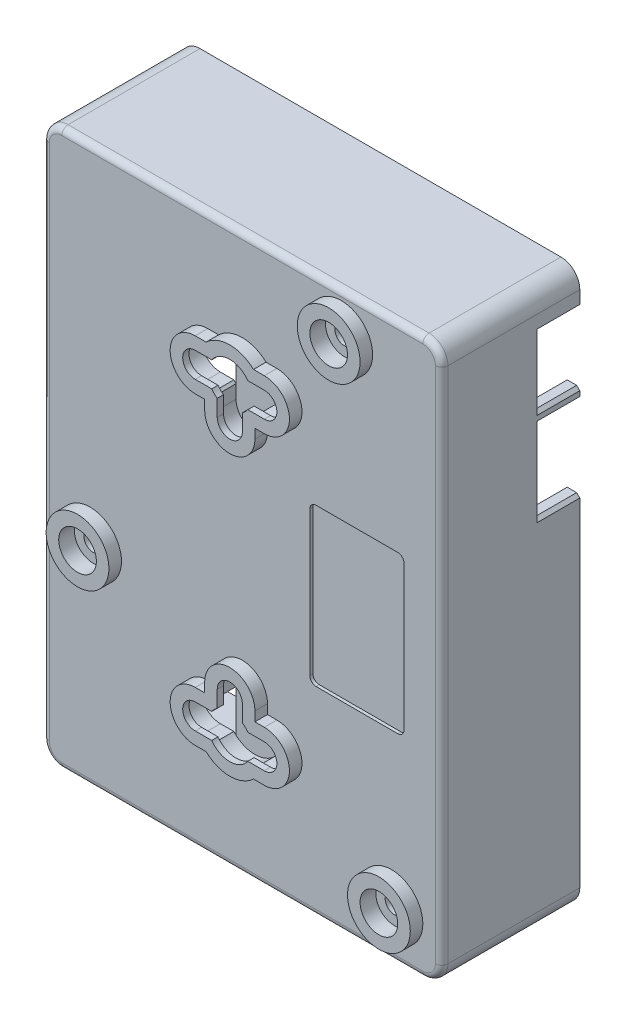
SolidWorks part; units mm, degrees
ref_plane "Front Plane" through (0, 0, 0) normal (0, 0, 1) x (1, 0, 0)
ref_plane "Top Plane" through (0, 0, 0) normal (0, 1, 0) x (1, 0, 0)
ref_plane "Right Plane" through (0, 0, 0) normal (1, 0, 0) x (0, 0, -1)
ref_plane "Plane1" through (0, 0, 2) normal (0, 0, 1) x (1, 0, 0)
sketch "Sketch2" plane through (0, 0, 2) normal (0, 0, 1) x (1, 0, 0)
  line L1 (-39.8212, 60.2968) -> (23.6788, 60.2968)
  line L2 (-39.8212, 60.2968) -> (-39.8212, -28.2032)
  line L3 (-39.8212, -28.2032) -> (23.6788, -28.2032)
  line L4 (23.6788, 60.2968) -> (23.6788, -28.2032)
  line L9 (20.6788, 57.2968) -> (20.6788, -25.2032) construction
  line L10 (20.6788, -25.2032) -> (-36.8212, -25.2032) construction
  line L11 (-36.8212, -25.2032) -> (-36.8212, 57.2968) construction
  line L12 (-36.8212, 57.2968) -> (20.6788, 57.2968) construction
  point P12 (0, 0)
  point P13 (0, 0)
  point P14 (0, 0)
  point P15 (0, 0)
  dimension "D1" = 3
  dimension "D2" = 3
  dimension "D3" = 3
  dimension "D4" = 3
extrude "Boss-Extrude1" add sketch "Sketch2" along normal blind 2
sketch "Sketch3" plane through (0, 0, 2) normal (0, 0, -1) x (-1, 0, 0)
  line L4 (39.8212, -28.2032) -> (39.8212, 60.2968)
  line L5 (39.8212, 60.2968) -> (-23.6788, 60.2968)
  line L6 (-23.6788, 60.2968) -> (-23.6788, -28.2032)
  line L7 (-23.6788, -28.2032) -> (39.8212, -28.2032)
  line L8 (39.8212, -28.2032) -> (39.8212, 60.2968)
  line L9 (39.8212, 60.2968) -> (-23.6788, 60.2968)
  line L10 (-23.6788, 60.2968) -> (-23.6788, -28.2032)
  line L11 (-23.6788, -28.2032) -> (39.8212, -28.2032)
  line L16 (37.8212, -26.2032) -> (37.8212, 58.2968)
  line L17 (37.8212, 58.2968) -> (-21.6788, 58.2968)
  line L18 (-21.6788, 58.2968) -> (-21.6788, -26.2032)
  line L19 (-21.6788, -26.2032) -> (37.8212, -26.2032)
  line L20 (37.8212, -26.2032) -> (37.8212, 58.2968)
  line L21 (37.8212, 58.2968) -> (-21.6788, 58.2968)
  line L22 (-21.6788, 58.2968) -> (-21.6788, -26.2032)
  line L23 (-21.6788, -26.2032) -> (37.8212, -26.2032)
  dimension "D1" = 0
  dimension "D2" = 2
extrude "Boss-Extrude2" add sketch "Sketch3" along normal blind 20
sketch "Sketch4" plane through (23.6788, 0, 0) normal (1, 0, 0) x (0, 0, -1)
  line L0 (18, 60.2968) -> (18, -28.2032) construction
  line L1 (18, 29.0468) -> (11.65, 29.0468)
  line L2 (18, 29.0468) -> (18, 42.0468)
  line L3 (18, 42.0468) -> (11.65, 42.0468)
  line L4 (11.65, 29.0468) -> (11.65, 42.0468)
  line L7 (18, 43.8468) -> (11.65, 43.8468)
  line L8 (18, 43.8468) -> (18, 54.7468)
  line L9 (18, 54.7468) -> (11.65, 54.7468)
  line L10 (11.65, 43.8468) -> (11.65, 54.7468)
  line L11 (16.95, 47.7968) -> (16.95, 50.7968) construction
  line L12 (16.95, 32.7968) -> (16.95, 38.2968) construction
  point P6 (0, 0)
  point P7 (0, 0)
  point P16 (16.95, 49.2968)
  point P17 (11.65, 49.2968)
  point P18 (16.95, 35.5468)
  point P19 (11.65, 35.5468)
  point P20 (0, 0)
  point P21 (0, 0)
  dimension "D1" = 10.9
  dimension "D2" = 13
extrude "Cut-Extrude1" cut sketch "Sketch4" against normal up to surface (2 mm away) up to face at (21.6788, 16.0468, -8)
chamfer "Chamfer1" distance 0.5 angle 45 6 edges at (23.6788, 54.7468, -14.825) (23.6788, 49.2968, -11.65) (23.6788, 43.8468, -14.825) (23.6788, 42.0468, -14.825) (23.6788, 35.5468, -11.65) (23.6788, 29.0468, -14.825)
sketch "Sketch5" plane through (-39.8212, 0, 0) normal (-1, 0, 0) x (0, 0, 1)
  line L0 (-18, -28.2032) -> (-18, 60.2968) construction
  line L1 (4, 60.2968) -> (-18, 60.2968) construction
  line L3 (-18, 34.207) -> (-11.65, 34.207)
  line L4 (-18, 34.207) -> (-18, 9.207)
  line L5 (-18, 9.207) -> (-11.65, 9.207)
  line L6 (-11.65, 34.207) -> (-11.65, 9.207)
  circle A0 centre (-12.432, 40.6543) radius 0.75
  point P12 (0, 0)
  dimension "D1" = 1.5
  dimension "D2" = 5.568
  dimension "D3" = 19.6425
  dimension "D4" = 25
extrude "Cut-Extrude3" cut sketch "Sketch5" against normal up to surface (2 mm away) up to face at (-37.8212, 16.0468, -8)
fillet "Fillet1" radius 6 2 edges at (-38.8212, 9.207, -18) (-38.8212, 34.207, -18)
sketch "Sketch6" plane through (0, -28.2032, 0) normal (0, -1, 0) x (1, 0, 0)
  line L0 (23.6788, -18) -> (-39.8212, -18) construction
  line L1 (13.0098, -18) -> (-13.7903, -18)
  line L2 (13.0098, -18) -> (13.0098, -11.65)
  line L3 (13.0098, -11.65) -> (-13.7903, -11.65)
  line L4 (-13.7903, -18) -> (-13.7903, -11.65)
  point P8 (0, 0)
extrude "Cut-Extrude4" cut sketch "Sketch6" against normal up to surface (2 mm away) up to face at (-8.0712, -26.2032, -8)
fillet "Fillet2" radius 3 4 edges at (-39.8212, 60.2968, -7) (23.6788, 60.2968, -7) (23.6788, -28.2032, -7) (-39.8212, -28.2032, -7)
sketch "Sketch7" plane through (0, 0, 4) normal (0, 0, 1) x (1, 0, 0)
  line L0 (-8.0712, -28.2032) -> (-8.0712, 60.2968) construction
  line L1 (-36.8212, -28.2032) -> (20.6788, -28.2032) construction
  line L2 (20.6788, 60.2968) -> (-36.8212, 60.2968) construction
  line L3 (-2.5712, -8.2032) -> (-13.5712, -8.2032) construction
  line L4 (-2.5712, -10.2032) -> (-5.199, -10.2032)
  line L5 (-2.5712, -6.2032) -> (-5.199, -6.2032)
  line L6 (23.6788, 16.0468) -> (-39.8212, 16.0468) construction
  line L7 (23.6788, -25.2032) -> (23.6788, 57.2968) construction
  line L8 (-39.8212, 57.2968) -> (-39.8212, -25.2032) construction
  line L9 (-10.0712, -2.7032) -> (-10.0712, -5.3309)
  line L10 (-6.0712, -2.7032) -> (-6.0712, -5.3309)
  line L11 (-10.9435, -6.2032) -> (-13.5712, -6.2032)
  line L12 (-10.9435, -10.2032) -> (-13.5712, -10.2032)
  line L13 (-6.0712, 34.7968) -> (-6.0712, 37.4245)
  line L14 (-2.5712, 38.2968) -> (-5.199, 38.2968)
  line L15 (-2.5712, 42.2968) -> (-5.199, 42.2968)
  line L16 (-10.9435, 42.2968) -> (-13.5712, 42.2968)
  line L17 (-10.9435, 38.2968) -> (-13.5712, 38.2968)
  line L18 (-10.0712, 34.7968) -> (-10.0712, 37.4245)
  arc A0 (-2.5712, -10.2032) -> (-2.5712, -6.2032) centre (-2.5712, -8.2032) ccw
  arc A1 (-13.5712, -6.2032) -> (-13.5712, -10.2032) centre (-13.5712, -8.2032) ccw
  arc A2 (-6.0712, -2.7032) -> (-10.0712, -2.7032) centre (-8.0712, -2.7032) ccw
  arc A3 (-10.0712, -5.3309) -> (-10.9435, -6.2032) centre (-8.0712, -8.2032) ccw
  arc A4 (-5.199, -6.2032) -> (-6.0712, -5.3309) centre (-8.0712, -8.2032) ccw
  arc A5 (-10.9435, -10.2032) -> (-5.199, -10.2032) centre (-8.0712, -8.2032) ccw
  arc A6 (-6.0712, 34.7968) -> (-10.0712, 34.7968) centre (-8.0712, 34.7968) cw
  arc A7 (-5.199, 38.2968) -> (-6.0712, 37.4245) centre (-8.0712, 40.2968) cw
  arc A8 (-2.5712, 42.2968) -> (-2.5712, 38.2968) centre (-2.5712, 40.2968) cw
  arc A9 (-10.9435, 42.2968) -> (-5.199, 42.2968) centre (-8.0712, 40.2968) cw
  arc A10 (-13.5712, 38.2968) -> (-13.5712, 42.2968) centre (-13.5712, 40.2968) cw
  arc A11 (-10.0712, 37.4245) -> (-10.9435, 38.2968) centre (-8.0712, 40.2968) cw
  point P8 (-8.0712, -8.2032)
  dimension "D4" = 4
  dimension "D6" = 7
  dimension "D1" = 11
  dimension "D2" = 4
  dimension "D3" = 20
  dimension "D5" = 5.5
extrude "Cut-Extrude5" cut sketch "Sketch7" against normal blind 10
sketch "Sketch8" plane through (0, 0, 4) normal (0, 0, 1) x (1, 0, 0)
  line L0 (-2.5712, 42.2968) -> (-5.199, 42.2968) construction
  line L1 (-5.199, 38.2968) -> (-2.5712, 38.2968) construction
  line L2 (-6.0712, 34.7968) -> (-6.0712, 37.4245) construction
  line L3 (-10.0712, 37.4245) -> (-10.0712, 34.7968) construction
  line L4 (-13.5712, 38.2968) -> (-10.9435, 38.2968) construction
  line L5 (-10.9435, 42.2968) -> (-13.5712, 42.2968) construction
  line L6 (-2.5712, 42.2968) -> (-5.199, 42.2968)
  line L7 (-5.199, 38.2968) -> (-2.5712, 38.2968)
  line L8 (-6.0712, 34.7968) -> (-6.0712, 37.4245)
  line L9 (-10.0712, 37.4245) -> (-10.0712, 34.7968)
  line L10 (-13.5712, 38.2968) -> (-10.9435, 38.2968)
  line L11 (-10.9435, 42.2968) -> (-13.5712, 42.2968)
  line L12 (-11.8462, 44.2968) -> (-13.5712, 44.2968)
  line L13 (-13.5712, 36.2968) -> (-12.0712, 36.2968)
  line L14 (-12.0712, 36.2968) -> (-12.0712, 34.7968)
  line L15 (-4.0712, 34.7968) -> (-4.0712, 36.2968)
  line L16 (-4.0712, 36.2968) -> (-2.5712, 36.2968)
  line L17 (-2.5712, 44.2968) -> (-4.2963, 44.2968)
  arc A0 (-2.5712, 38.2968) -> (-2.5712, 42.2968) centre (-2.5712, 40.2968) ccw construction
  arc A1 (-6.0712, 37.4245) -> (-5.199, 38.2968) centre (-8.0712, 40.2968) ccw construction
  arc A2 (-10.0712, 34.7968) -> (-6.0712, 34.7968) centre (-8.0712, 34.7968) ccw construction
  arc A3 (-10.9435, 38.2968) -> (-10.0712, 37.4245) centre (-8.0712, 40.2968) ccw construction
  arc A4 (-13.5712, 42.2968) -> (-13.5712, 38.2968) centre (-13.5712, 40.2968) ccw construction
  arc A5 (-5.199, 42.2968) -> (-10.9435, 42.2968) centre (-8.0712, 40.2968) ccw construction
  arc A6 (-2.5712, 38.2968) -> (-2.5712, 42.2968) centre (-2.5712, 40.2968) ccw
  arc A7 (-6.0712, 37.4245) -> (-5.199, 38.2968) centre (-8.0712, 40.2968) ccw
  arc A8 (-10.0712, 34.7968) -> (-6.0712, 34.7968) centre (-8.0712, 34.7968) ccw
  arc A9 (-10.9435, 38.2968) -> (-10.0712, 37.4245) centre (-8.0712, 40.2968) ccw
  arc A10 (-13.5712, 42.2968) -> (-13.5712, 38.2968) centre (-13.5712, 40.2968) ccw
  arc A11 (-5.199, 42.2968) -> (-10.9435, 42.2968) centre (-8.0712, 40.2968) ccw
  arc A12 (-4.2963, 44.2968) -> (-11.8462, 44.2968) centre (-8.0712, 40.2968) ccw
  arc A13 (-13.5712, 44.2968) -> (-13.5712, 36.2968) centre (-13.5712, 40.2968) ccw
  arc A14 (-12.0712, 36.2968) -> (-12.0712, 36.2968) centre (-12.0712, 36.2968) cw
  arc A15 (-12.0712, 34.7968) -> (-4.0712, 34.7968) centre (-8.0712, 34.7968) ccw
  arc A16 (-4.0712, 36.2968) -> (-4.0712, 36.2968) centre (-4.0712, 36.2968) cw
  arc A17 (-2.5712, 36.2968) -> (-2.5712, 44.2968) centre (-2.5712, 40.2968) ccw
  dimension "D1" = 2
extrude "Boss-Extrude3" add sketch "Sketch8" along normal blind 2
sketch "Sketch9" plane through (0, 0, 2) normal (0, 0, -1) x (-1, 0, 0)
  circle A0 centre (-15.6788, -20.7032) radius 3.5
  circle A1 centre (32.3212, 5.2968) radius 3.5
  circle A2 centre (-7.6788, 53.7968) radius 2.5
  point P9 (0, 0)
  point P10 (0, 0)
  point P11 (0, 0)
  point P12 (0, 0)
  dimension "D1" = 7
  dimension "D2" = 7
  dimension "D3" = 5
extrude "Boss-Extrude4" add sketch "Sketch9" along normal up to surface (12.05 mm away)
sketch "Sketch10" plane through (0, 0, 4) normal (0, 0, 1) x (1, 0, 0)
  circle A0 centre (7.6788, 53.7968) radius 1.5
  circle A1 centre (15.6788, -20.7032) radius 1.5
  circle A2 centre (-32.3212, 5.2968) radius 1.5
  dimension "D1" = 3
extrude "Cut-Extrude6" cut sketch "Sketch10" against normal through all
sketch "Sketch11" plane through (0, 0, 4) normal (0, 0, 1) x (1, 0, 0)
  circle A0 centre (7.6788, 53.7968) radius 3
  circle A2 centre (-32.3212, 5.2968) radius 3
  circle A3 centre (15.6788, -20.7032) radius 3
  dimension "D1" = 6
extrude "Cut-Extrude7" cut sketch "Sketch11" against normal blind 0.5
sketch "Sketch12" plane through (0, 0, 4) normal (0, 0, 1) x (1, 0, 0)
  circle A0 centre (15.6788, -20.7032) radius 3 construction
  circle A1 centre (-32.3212, 5.2968) radius 3 construction
  circle A2 centre (7.6788, 53.7968) radius 3 construction
  circle A3 centre (15.6788, -20.7032) radius 3
  circle A4 centre (-32.3212, 5.2968) radius 3
  circle A5 centre (7.6788, 53.7968) radius 3
  circle A6 centre (7.6788, 53.7968) radius 5
  circle A7 centre (-32.3212, 5.2968) radius 5
  circle A8 centre (15.6788, -20.7032) radius 5
  dimension "D1" = 2
extrude "Boss-Extrude5" add sketch "Sketch12" along normal blind 2
sketch "Sketch13" plane through (0, 0, 2) normal (0, 0, -1) x (-1, 0, 0)
  line L44 (13.5712, 43.2968) -> (11.4253, 43.2968)
  line L45 (11.4253, 37.2968) -> (13.5712, 37.2968)
  line L46 (11.0712, 34.7968) -> (11.0712, 36.9427)
  line L47 (5.0712, 36.9427) -> (5.0712, 34.7968)
  line L48 (2.5712, 37.2968) -> (4.7171, 37.2968)
  line L49 (4.7171, 43.2968) -> (2.5712, 43.2968)
  line L50 (13.5712, 43.2968) -> (11.4253, 43.2968)
  line L51 (11.4253, 37.2968) -> (13.5712, 37.2968)
  line L52 (11.0712, 34.7968) -> (11.0712, 36.9427)
  line L53 (5.0712, 36.9427) -> (5.0712, 34.7968)
  line L54 (2.5712, 37.2968) -> (4.7171, 37.2968)
  line L55 (4.7171, 43.2968) -> (2.5712, 43.2968)
  arc A50 (13.5712, 37.2968) -> (13.5712, 43.2968) centre (13.5712, 40.2968) ccw
  arc A51 (11.0712, 36.9427) -> (11.4253, 37.2968) centre (8.0712, 40.2968) ccw
  arc A52 (5.0712, 34.7968) -> (11.0712, 34.7968) centre (8.0712, 34.7968) ccw
  arc A53 (4.7171, 37.2968) -> (5.0712, 36.9427) centre (8.0712, 40.2968) ccw
  arc A54 (2.5712, 43.2968) -> (2.5712, 37.2968) centre (2.5712, 40.2968) ccw
  arc A55 (11.4253, 43.2968) -> (4.7171, 43.2968) centre (8.0712, 40.2968) ccw
  arc A56 (13.5712, 37.2968) -> (13.5712, 43.2968) centre (13.5712, 40.2968) ccw
  arc A57 (11.0712, 36.9427) -> (11.4253, 37.2968) centre (8.0712, 40.2968) ccw
  arc A58 (5.0712, 34.7968) -> (11.0712, 34.7968) centre (8.0712, 34.7968) ccw
  arc A59 (4.7171, 37.2968) -> (5.0712, 36.9427) centre (8.0712, 40.2968) ccw
  arc A60 (2.5712, 43.2968) -> (2.5712, 37.2968) centre (2.5712, 40.2968) ccw
  arc A61 (11.4253, 43.2968) -> (4.7171, 43.2968) centre (8.0712, 40.2968) ccw
  dimension "D1" = 1
extrude "Cut-Extrude8" cut sketch "Sketch13" against normal blind 3
ref_plane "Plane2" through (0, 16.0468, 0) normal (0, 1, 0) x (1, 0, 0)
mirror "Mirror1" about plane through (0, 16.0468, 0) normal (0, 1, 0) of "Cut-Extrude8", "Boss-Extrude3"
ref_plane "Plane3" through (-8.0712, 0, 0) normal (1, 0, 0) x (0, 0, -1)
sketch "Sketch14" plane through (-8.0712, 0, 0) normal (1, 0, 0) x (0, 0, -1)
  line L0 (-2, 48.7968) -> (2, 48.7968)
  line L1 (-2, -26.2032) -> (-2, 58.2968) construction
  line L2 (2, 48.7968) -> (2, 27.7968)
  line L3 (2, 27.7968) -> (-2, 27.7968)
  line L4 (-2, 27.7968) -> (-2, 29.7968)
  line L5 (-2, 29.7968) -> (0, 29.7968)
  line L6 (0, 29.7968) -> (0, 46.7968)
  line L7 (0, 46.7968) -> (-2, 46.7968)
  line L8 (-2, 46.7968) -> (-2, 48.7968)
  line L9 (-6, 45.7968) -> (-6, 30.7968) construction
  line L10 (-6, 45.7968) -> (-6, 44.2968) construction
  line L11 (-6, 34.7968) -> (-6, 30.7968) construction
  point P16 (0, 38.2968)
  dimension "D1" = 2
  dimension "D2" = 2
  dimension "D3" = 2
  dimension "D4" = 2
  dimension "D5" = 17
extrude "Boss-Extrude6" add sketch "Sketch14" along normal mid plane 10
fillet "Fillet3" radius 2 4 edges at (-8.0712, 27.7968, 2) (-8.0712, 27.7968, -2) (-8.0712, 48.7968, 2) (-8.0712, 48.7968, -2)
mirror "Mirror2" about plane through (0, 16.0468, 0) normal (0, 1, 0) of "Fillet3", "Boss-Extrude6"
fillet "Fillet4" radius 1 8 edges at (22.8001, 59.4181, 4) (23.6788, 16.0468, 4) (22.8001, -27.3245, 4) (-8.0712, -28.2032, 4) (-38.9426, -27.3245, 4) (-39.8212, 16.0468, 4) (-38.9426, 59.4181, 4) (-8.0712, 60.2968, 4)
sketch "Sketch15" plane through (0, 0, 4) normal (0, 0, 1) x (1, 0, 0)
  line L0 (-38.8212, 16.0468) -> (22.6788, 16.0468) construction
  line L1 (3.6788, 28.5468) -> (16.6788, 28.5468)
  line L2 (2.6788, 27.5468) -> (2.6788, 4.5468)
  line L3 (3.6788, 3.5468) -> (16.6788, 3.5468)
  line L4 (17.6788, 27.5468) -> (17.6788, 4.5468)
  line L5 (-38.8212, 57.2968) -> (-38.8212, -25.2032) construction
  line L6 (22.6788, -25.2032) -> (22.6788, 57.2968) construction
  arc A0 (3.6788, 3.5468) -> (2.6788, 4.5468) centre (3.6788, 4.5468) cw
  arc A1 (17.6788, 4.5468) -> (16.6788, 3.5468) centre (16.6788, 4.5468) cw
  arc A2 (17.6788, 27.5468) -> (16.6788, 28.5468) centre (16.6788, 27.5468) ccw
  arc A3 (2.6788, 27.5468) -> (3.6788, 28.5468) centre (3.6788, 27.5468) cw
  point P10 (17.6788, 16.0468)
  point P13 (2.6788, 3.5468)
  point P18 (17.6788, 28.5468)
  point P21 (2.6788, 28.5468)
  dimension "D4" = 1
  dimension "D1" = 25
  dimension "D2" = 15
  dimension "D3" = 5
extrude "Cut-Extrude9" cut sketch "Sketch15" against normal blind 0.5
